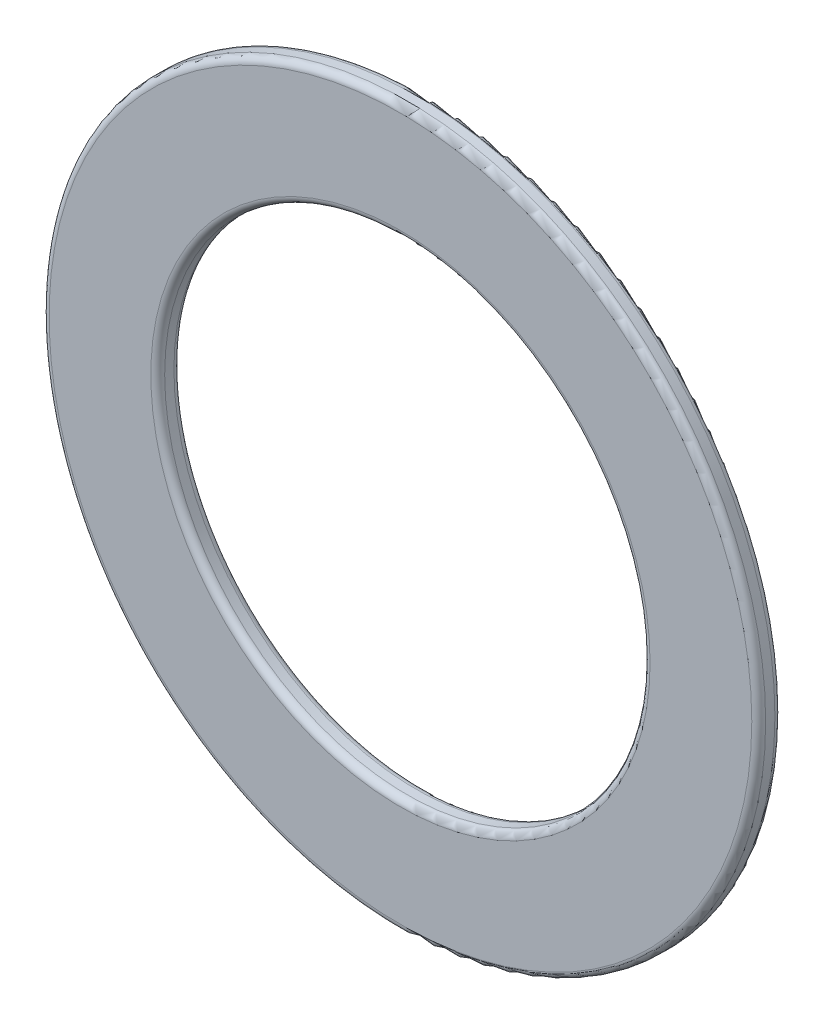
SolidWorks part; units mm, degrees
ref_plane "Front Plane" through (0, 0, 0) normal (0, 0, 1) x (1, 0, 0)
ref_plane "Top Plane" through (0, 0, 0) normal (0, 1, 0) x (1, 0, 0)
ref_plane "Right Plane" through (0, 0, 0) normal (1, 0, 0) x (0, 0, -1)
sketch "Sketch1" plane through (0, 0, 0) normal (0, 0, 1) x (1, 0, 0)
  circle A0 centre (0, 0) radius 5.25
  circle A1 centre (0, 0) radius 7.75
  dimension "D1" = 10.5
  dimension "D2" = 2.5
base flange "Base-Flange1" sketch "Sketch1" thickness 0.5 reverse thickness direction no parameters "D1"=1
fillet "Fillet1" radius 0.15 4 edges at (5.25, 0, 0) (5.25, 0, -0.5) (7.75, 0, 0) (7.75, 0, -0.5)
sketch "Bend-Lines1" [suppressed] plane through (0, 0, 0) normal (0, 1, 0) x (1, 0, 0)
sketch "Bounding-Box1" [suppressed] plane through (0, 0, 0) normal (0, 1, 0) x (1, 0, 0)
sheet metal parameters "Sheet-Metal1" thickness 0.5 parameters "D1"=1
flat pattern "Flat-Pattern1" [suppressed]
sketch "Bend-Lines2" plane through (0, 0, 0) normal (0, 1, 0) x (1, 0, 0)
sketch3d "Bounding-Box2" [suppressed]
  line L0 (-7.75, -7.75, 0) -> (7.75, -7.75, 0) construction
  line L1 (-7.75, 7.75, 0) -> (7.75, 7.75, 0) construction
  line L2 (-7.75, -7.75, 0) -> (-7.75, 7.75, 0) construction
  line L3 (7.75, -7.75, 0) -> (7.75, 7.75, 0) construction
